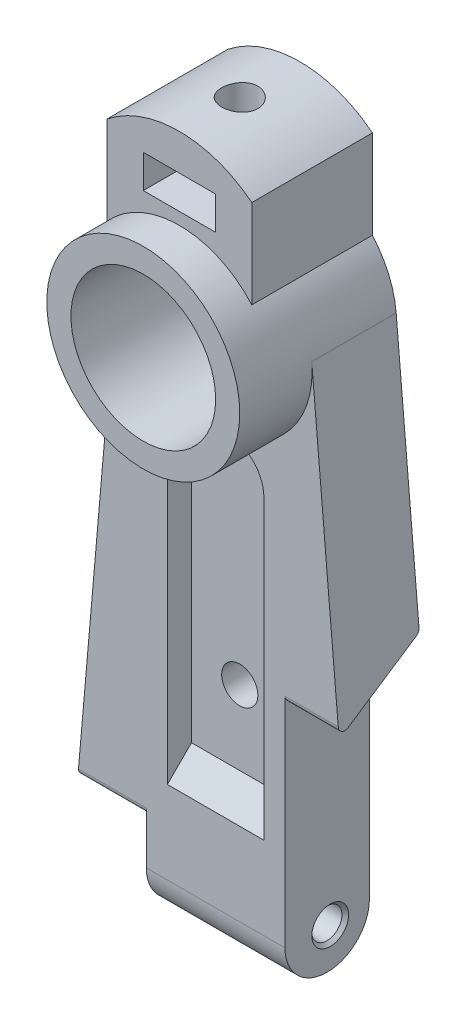
SolidWorks part; units mm, degrees
ref_plane "Front Plane" through (0, 0, 0) normal (0, 0, 1) x (1, 0, 0)
ref_plane "Top Plane" through (0, 0, 0) normal (0, 1, 0) x (1, 0, 0)
ref_plane "Right Plane" through (0, 0, 0) normal (1, 0, 0) x (0, 0, -1)
sketch "Sketch1" plane through (0, 0, 0) normal (1, 0, 0) x (0, 0, -1)
  line L1 (-3.5, 19) -> (3.5, 19)
  line L2 (-3.5, 19) -> (-3.5, -23.51)
  line L3 (-3.5, -23.51) -> (3.5, -23.51) construction
  line L4 (3.5, 19) -> (3.5, -23.51)
  line L5 (-3.5, 19) -> (3.5, -23.51) construction
  line L6 (-3.5, -23.51) -> (3.5, 19) construction
  arc A0 (-3.5, -23.51) -> (3.5, -23.51) centre (0, -23.51) ccw
  circle A1 centre (0.25, -23.76) radius 1
  point P0 (0, -2.255)
  dimension "D4" = 2
  dimension "D1" = 19
  dimension "D2" = 23.51
  dimension "D3" = 7
  dimension "D5" = 0.25
  dimension "D6" = 0.25
extrude "Boss-Extrude1" add sketch "Sketch1" along normal mid plane 11.5
sketch "Sketch3" plane through (0, 0, 0) normal (0, 0, 1) x (1, 0, 0)
  line L0 (0, -27.01) -> (0, 33.75) construction
  line L1 (6, 24.2915) -> (6, 31.6415)
  line L2 (-3, 30.75) -> (3, 30.75)
  line L3 (3, 30.75) -> (3, 28)
  line L4 (3, 28) -> (-3, 28)
  line L5 (0, 27) -> (0, 28) construction
  line L6 (0, 33.75) -> (-1.4424, 33.75) construction
  line L7 (-4, 12.0718) -> (-4, -14.65)
  line L8 (-3, 30.75) -> (-3, 28)
  line L9 (-6, 24.2915) -> (-6, 31.6415)
  line L10 (-5.75, -27.01) -> (5.75, -27.01) construction
  line L11 (-4, 11) -> (4, 11)
  line L13 (-4, -14.65) -> (4, -14.65)
  line L14 (4, 12.0718) -> (4, -14.65)
  circle A0 centre (0, 19) radius 8
  circle A1 centre (0, 19) radius 6
  arc A2 (6, 31.6415) -> (-6, 31.6415) centre (0, 24.1589) ccw
  circle A3 centre (0, -8.5) radius 1.5
  point P20 (0, -14.65)
  point P27 (0, 30.75)
  dimension "D1" = 16
  dimension "D2" = 12
  dimension "D5" = 6
  dimension "D12" = 3
  dimension "D3" = 19
  dimension "D4" = 7.35
  dimension "D6" = 3
  dimension "D7" = 2.75
  dimension "D8" = 3
  dimension "D9" = 1
  dimension "D10" = 8
  dimension "D11" = 25.65
  dimension "D13" = 8.5
extrude "Boss-Extrude2" add sketch "Sketch3" along normal blind 6.5 and the other way blind 3.5 separate body contours L1 A2 L2 L3 L4 A0 region at (0, 27.1528, 0)
extrude "Boss-Extrude3" add sketch "Sketch3<5>" along normal blind 9.5 and the other way blind 3.5 contours A0 A1 region at (7.2717, 21.7484, 0)
sketch "Sketch3<5>" plane through (0, 0, 0) normal (0, 0, 1) x (1, 0, 0) same geometry as "Sketch3"
extrude "Cut-Extrude1" cut sketch "Sketch3<6>" against normal through all both and the other way through all contours A1 | A3 region at (0, 19, 0) region at (0, -8.5, 0)
sketch "Sketch3<6>" plane through (0, 0, 0) normal (0, 0, 1) x (1, 0, 0) same geometry as "Sketch3"
extrude "Cut-Extrude3" cut sketch "Sketch3<8>" along normal blind 2 from offset 1.5 contours L14 L11 L7 L13 A3 region at (0, -1.5869, 0)
sketch "Sketch3<8>" plane through (0, 0, 0) normal (0, 0, 1) x (1, 0, 0) same geometry as "Sketch3"
fillet "Fillet1" radius 3 2 edges at (-4, 11, 2.5) (4, 11, 2.5)
chamfer "Chamfer1" distance 2 angle 45 1 edges at (0, -14.65, 3.5)
sketch "Sketch6" plane through (0, 0, 0) normal (0, 0, 1) x (1, 0, 0)
  line L0 (-5.75, -20) -> (-11.4426, -20)
  line L1 (-5.75, 13.4379) -> (-5.75, -23.51) construction
  line L2 (-11.4426, -20) -> (-7.9696, 19.6972)
  line L4 (10.244, -6.3) -> (7.9696, 19.6972)
  line L5 (5.75, 13.4379) -> (5.75, -23.51) construction
  line L6 (10.244, -6.3) -> (5.75, -6.3)
  line L7 (-5.75, -20) -> (-5.75, 13.4379)
  line L8 (5.75, -6.3) -> (5.75, 13.4379)
  circle A0 centre (0, 19) radius 8 construction
  circle A1 centre (0, 19) radius 8 construction
  arc A2 (-5.75, 13.4379) -> (-7.9696, 19.6972) centre (0, 19) cw
  arc A3 (5.75, 13.4379) -> (7.9696, 19.6972) centre (0, 19) ccw
  dimension "D1" = 20
  dimension "D2" = 5
  dimension "D3" = 6.3
  dimension "D4" = 5
extrude "Boss-Extrude4" add sketch "Sketch6" along normal mid plane 7 contours L7 A2 L2 L0 | A3 L8 L6 L4 region at (-7.9355, -4.4618, 0) region at (7.598, 3.645, 0)
ref_plane "Plane1" through (10.244, 0, 0) normal (1, 0, 0) x (0, 0, -1)
sketch "Sketch8" plane through (10.244, 0, 0) normal (1, 0, 0) x (0, 0, -1)
  line L0 (-3.5, -6.3) -> (3.5, -2.2585)
  line L1 (3.5, -6.3) -> (3.5, 19.6972) construction
  line L2 (3.5, -2.2585) -> (3.5, -6.3)
  line L3 (3.5, -6.3) -> (-3.5, -6.3)
  dimension "D1" = 60
extrude "Cut-Extrude5" cut sketch "Sketch8" against normal up to surface (4.494 mm away) up to face at (5.75, -15.78, 0)
ref_plane "Plane2" through (-11.4426, 0, 0) normal (-1, 0, 0) x (0, 0, 1)
sketch "Sketch9" plane through (-11.4426, 0, 0) normal (-1, 0, 0) x (0, 0, 1)
  line L0 (-3.5, -20) -> (-3.5, -16.7358)
  line L2 (-3.5, -16.7358) -> (3.5, -20)
  line L3 (3.5, -20) -> (-3.5, -20)
  dimension "D1" = 65
extrude "Cut-Extrude6" cut sketch "Sketch9" against normal up to surface (5.6926 mm away) up to face at (-5.75, -22.63, 0)
fillet "Fillet2" radius 0.5 4 edges at (7.997, -6.3, 3.5) (7.8202, -2.2585, -3.5) (-8.4535, -16.7358, -3.5) (-8.5963, -20, 3.5)
sketch "Sketch11" plane through (0, 28, 0) normal (0, 1, 0) x (1, 0, 0)
  line L4 (-3, 3.5) -> (-3, -6.5)
  line L5 (-3, -6.5) -> (3, -6.5)
  line L6 (3, -6.5) -> (3, 3.5)
  line L7 (3, 3.5) -> (-3, 3.5)
  line L8 (-3, 3.5) -> (-3, -6.5) construction
  line L9 (-3, -6.5) -> (3, -6.5) construction
  line L10 (3, -6.5) -> (3, 3.5) construction
  line L11 (3, 3.5) -> (-3, 3.5) construction
  circle A0 centre (0, -1.5) radius 1.5
  point P7 (-3, -1.5)
  dimension "D2" = 3
  dimension "D1" = 0
extrude "Cut-Extrude8" cut sketch "Sketch11" along normal through all and the other way blind 10
hole_wizard "M3 Tapped Hole1" positions "Sketch12" profile "Sketch13" tap size "M3" standard "ISO"
sketch "Sketch12" plane through (-9.6192, 0.8416, 0) normal (-0.9962, 0.0872, 0) x (0, 0, 1)
  point P0 (0, 0)
sketch "Sketch13" plane through (-9.6192, 0.8416, 0) normal (0, 0, 1) x (-0.0872, -0.9962, 0)
  line L0 (0, 0) -> (0, 7.8511)
  line L1 (0, 7.8511) -> (1.25, 7.1)
  line L2 (1.25, 7.1) -> (1.25, 0.275)
  line L3 (1.25, 0.275) -> (1.525, 0)
  line L5 (1.525, 0) -> (0, 0)
  line L6 (-1.25, 0.275) -> (-1.525, 0) construction
  line L10 (0, 7.8511) -> (-1.25, 7.1) construction
  line L11 (0, -6.35) -> (0, 107.95) construction
  dimension "Tap Drill Dia." = 2.5
  dimension "Tap Drill Depth" = 7.1
  dimension "Near C'Sink Dia." = 3.05
  dimension "Near C'Sink Angle" = 90
  dimension "Drill Angle" = 118
cosmetic thread "Hole Thread1" parameters "D1"=4.6, "D2"=3
pattern_linear "LPattern1" count 2 spacing 5 along (-0.0872, -0.9962, 0) of "M3 Tapped Hole1"
sketch "Sketch14" plane through (-5.75, 0, 0) normal (-1, 0, 0) x (0, 0, 1)
  circle A0 centre (-0.25, -23.76) radius 1 construction
  circle A1 centre (-0.25, -23.76) radius 1
extrude "Boss-Extrude5" add sketch "Sketch14" against normal up to surface (11.5 mm away) up to face at (5.75, -11.074, -0.0722)
hole_wizard "M3 Tapped Hole2" positions "Sketch15" profile "Sketch16" tap size "M3" standard "ISO" end condition through all
sketch "Sketch15" plane through (-5.75, 0, 0) normal (-1, 0, 0) x (0, 0, 1)
  point P0 (-0.25, -23.76)
sketch "Sketch16" plane through (-5.75, -23.76, -0.25) normal (0, 1, 0) x (0, 0, 1)
  line L0 (0, 0) -> (0, 11.5)
  line L1 (0, 11.5) -> (1.525, 11.5)
  line L2 (1.25, 11.225) -> (1.25, 0.275)
  line L3 (1.25, 0.275) -> (1.525, 0)
  line L5 (1.525, 0) -> (0, 0)
  line L6 (-1.25, 0.275) -> (-1.525, 0) construction
  line L7 (1.525, 11.5) -> (1.25, 11.225)
  line L8 (-1.525, 11.5) -> (-1.25, 11.225) construction
  line L11 (0, -6.35) -> (0, 107.95) construction
  dimension "Thru Tap Drill Dia." = 2.5
  dimension "Thru Tap Drill Depth" = 11.5
  dimension "Near C'Sink Dia." = 3.05
  dimension "Near C'Sink Angle" = 90
  dimension "Far C'Sink Dia." = 3.05
  dimension "Far C'Sink Angle" = 90
cosmetic thread "Hole Thread2" parameters "D2"=3
